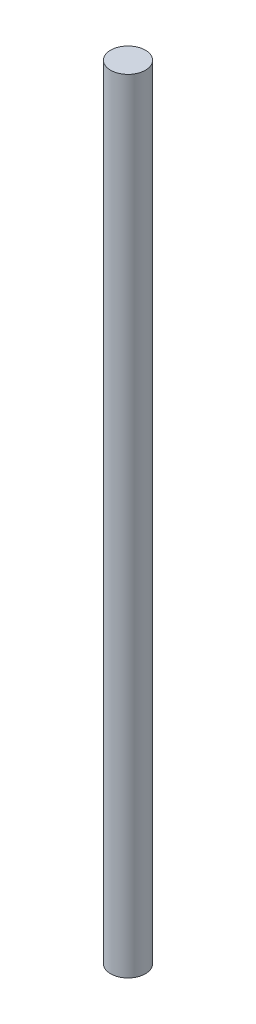
SolidWorks part; units mm, degrees
ref_plane "Płaszczyzna przednia" through (0, 0, 0) normal (0, 0, 1) x (1, 0, 0)
ref_plane "Płaszczyzna górna" through (0, 0, 0) normal (0, 1, 0) x (1, 0, 0)
ref_plane "Płaszczyzna prawa" through (0, 0, 0) normal (1, 0, 0) x (0, 0, -1)
sketch "Szkic1" plane through (0, 0, 0) normal (0, 1, 0) x (1, 0, 0)
  circle A0 centre (0, 0) radius 1
extrude "Dodanie-wyciągnięcie1" add sketch "Szkic1" along normal blind 45
